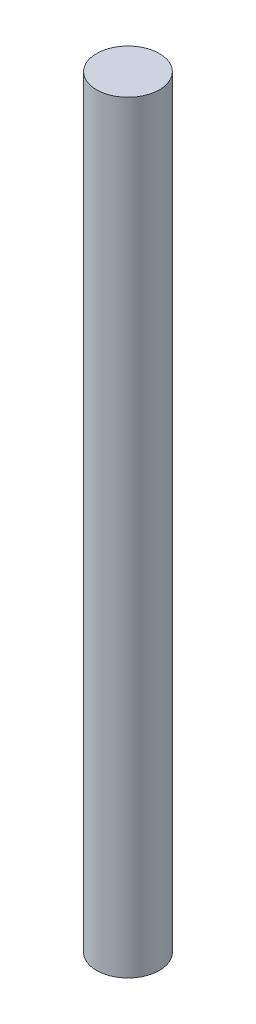
SolidWorks part; units mm, degrees
ref_plane "Front Plane" through (0, 0, 0) normal (0, 0, 1) x (1, 0, 0)
ref_plane "Top Plane" through (0, 0, 0) normal (0, 1, 0) x (1, 0, 0)
ref_plane "Right Plane" through (0, 0, 0) normal (1, 0, 0) x (0, 0, -1)
sketch "Elevation Bar" plane through (0, 0, 0) normal (0, 1, 0) x (1, 0, 0)
  circle A0 centre (0, 0) radius 30.226
  dimension "D1" = 60.452
extrude "Elevation Bar Part" add sketch "Elevation Bar" along normal blind 734.06
sketch "Sketch2" plane through (0, 0, 0) normal (0, 0, 1) x (1, 0, 0)
  line L0 (0, 0) -> (172.1794, 0) construction
  line L1 (-30.226, 0) -> (-30.226, 734.06) construction
  line L2 (-30.226, 734.06) -> (30.226, 734.06) construction
  line L3 (30.226, 734.06) -> (30.226, 0) construction
  line L4 (30.226, 0) -> (30.226, 734.06) construction
sketch "Sketch3" plane through (0, 0, 0) normal (1, 0, 0) x (0, 0, -1)
  line L0 (-30.226, 0) -> (30.226, 0) construction
  line L1 (33.2486, 0) -> (-33.2486, 0) construction
  line L2 (-30.226, 459.74) -> (30.226, 459.74) construction
  line L3 (-30.226, 642.62) -> (30.226, 642.62) construction
  line L4 (-30.226, 0) -> (30.226, 0) construction
  line L5 (-30.226, 0) -> (-30.226, 734.06) construction
  line L6 (-30.226, 734.06) -> (30.226, 734.06) construction
  line L7 (30.226, 0) -> (30.226, 734.06) construction
  line L8 (-30.226, 551.18) -> (30.226, 551.18) construction
  line L9 (30.226, 0) -> (381.4546, 0) construction
  line L10 (91.4292, 22.0181) -> (428.854, 22.0181)
  point P6 (0, 0)
  dimension "D1" = 91.44
  dimension "D2" = 91.44
  dimension "D3" = 91.44
  dimension "D4" = 337.4248
equation "\"D2@Sketch3\"=\"D1@Sketch3\""
equation "\"D3@Sketch3\"=\"D1@Sketch3\""
